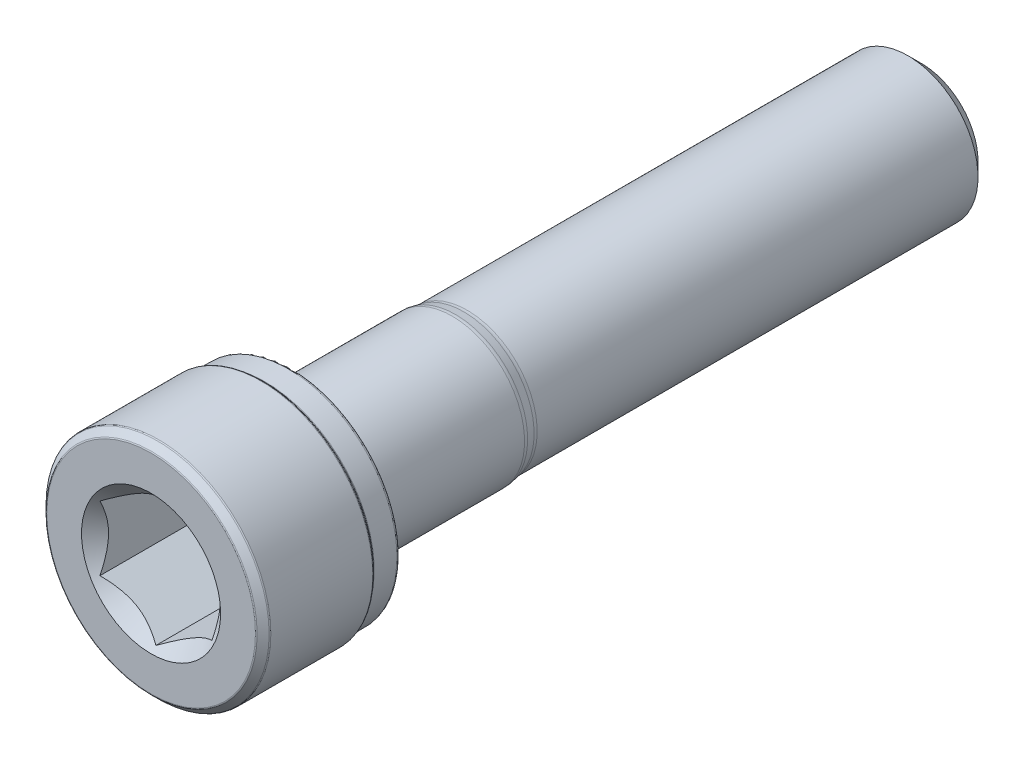
SolidWorks part; units mm, degrees
ref_plane "Front Plane" through (0, 0, 0) normal (0, 0, 1) x (1, 0, 0)
ref_plane "Top Plane" through (0, 0, 0) normal (0, 1, 0) x (1, 0, 0)
ref_plane "Right Plane" through (0, 0, 0) normal (1, 0, 0) x (0, 0, -1)
sketch "Sketch1" plane through (0, 0, 0) normal (1, 0, 0) x (0, 0, -1)
  line L0 (-27.5, 0) -> (27.5, 0) construction
  line L1 (27.5, 0) -> (27.5, 4.0257) construction
  line L2 (27.5, 4.0257) -> (26.5257, 5) construction
  line L3 (26.5257, 5) -> (26.375, 5) construction
  line L4 (26.375, 5) -> (-17.5, 5) construction
  line L5 (-17.5, 5) -> (-17.5, 8) construction
  line L6 (-17.5, 8) -> (-27.5, 8) construction
  line L7 (-27.5, 8) -> (-27.5, 0) construction
  line L8 (27.5, 4.0257) -> (27.5, 5) construction
  line L9 (27.4062, 5.1624) -> (28.1562, 3.8633) construction
  line L10 (28.1562, 3.8633) -> (28.9062, 5.1624) construction
  line L11 (28.9062, 5.1624) -> (27.4062, 5.1624) construction
  line L12 (28.1562, 5.1624) -> (28.1562, 5) construction
  line L13 (28.1562, 3.8633) -> (28.1562, 4.0257) construction
  line L14 (28.0625, 4.0257) -> (28.25, 4.0257) construction
  line L15 (27.5, 5) -> (28.8125, 5) construction
  line L16 (27.4531, 5.0812) -> (28.8594, 5.0812) construction
  line L17 (27.5, 0) -> (27.5, -5) construction
  line L18 (-18, 8) -> (-17.5, 7.5) construction
  line L19 (-27, 8) -> (-27.5, 7.5) construction
  line L20 (-17.5, 5) -> (-17.5, 0) construction
  line L21 (-17.5, 2.5) -> (-2.5, 2.5) construction
  line L22 (-2.5, 2.5) -> (12.5, 2.5) construction
  line L23 (12.5, 2.5) -> (27.5, 2.5) construction
  line L24 (-2.5, 2.5) -> (-2.5, 5) construction
  line L25 (-2.5, 5) -> (-2.5, 8) construction
  line L26 (12.5, 2.5) -> (12.5, 8) construction
  point P0 (-27.5, 4)
  point P3 (23.75, 5)
  point P4 (0, 0)
  point P18 (12.5, 5)
  point P22 (28.1562, 4.0257)
  point P24 (26.375, 5)
  point P25 (28.1562, 5)
  point P28 (28.1563, 5.0812)
  point P29 (23.75, -5)
  point P30 (-2.5, 5)
  point P31 (-22.5, 8)
  point P37 (-19.25, 8)
  point P38 (-26.75, 8)
  point P45 (-2.5, 2.5)
  point P46 (12.5, 2.5)
  point P49 (-4.5, 5)
  dimension "D1" = 45
  dimension "D2" = 0.1875
  dimension "D7" = 0.5
  dimension "D8" = 0.5
  dimension "D9" = 0.5
  dimension "D10" = 0.25
  dimension "D11" = 1.25
  dimension "Drive Size" = 8
  dimension "Head Diameter" = 16
  dimension "Head Height" = 10
  dimension "Thread Pitch" = 1.5
  dimension "Thread Dia" = 10
  dimension "Length" = 45
  dimension "D12" = 1.125
  dimension "D4" = 3.75
  dimension "Minimum Thread Length" = 32
sketch "Sketch2" plane through (0, 0, 0) normal (1, 0, 0) x (0, 0, -1)
  line L0 (-27.5, 0) -> (-27.5, 7.4482)
  line L1 (-26.9482, 8) -> (-19.6768, 8)
  line L2 (-17.5, 7.55) -> (-17.5, 5.6624)
  line L4 (26.5257, 5) -> (27.5, 4.0257)
  line L5 (27.5, 4.0257) -> (27.5, 0)
  line L6 (-17.5, 8) -> (-27.5, 8) construction
  line L7 (27.5, 0) -> (-27.5, 0)
  line L8 (-27, 8) -> (-27.5, 7.5) construction
  line L10 (-27.0366, 7.9634) -> (-27.4634, 7.5366)
  line L12 (-19.3232, 7.75) -> (-17.7, 7.75)
  line L14 (-18, 8) -> (-17.5, 7.5) construction
  line L15 (-19.5884, 7.9634) -> (-19.4116, 7.7866)
  line L17 (-17.5, 5) -> (-17.5, 8) construction
  line L18 (-17, 5.1624) -> (-6.002, 5.1624)
  line L19 (-4.9394, 5) -> (26.5257, 5)
  line L20 (26.375, 5) -> (-17.5, 5) construction
  line L21 (-5.7581, 5.1384) -> (-5.1832, 5.024)
  line L22 (28.9062, 5.1624) -> (27.4062, 5.1624) construction
  arc A0 (-17.7, 7.75) -> (-17.5, 7.55) centre (-17.7, 7.55) cw
  arc A1 (-17.5, 5.6624) -> (-17, 5.1624) centre (-17, 5.6624) ccw
  arc A2 (-6.002, 5.1624) -> (-5.7581, 5.1384) centre (-6.002, 3.9124) cw
  arc A3 (-5.1832, 5.024) -> (-4.9394, 5) centre (-4.9394, 6.25) ccw
  arc A4 (-27.0366, 7.9634) -> (-26.9482, 8) centre (-26.9482, 7.875) cw
  arc A5 (-27.4634, 7.5366) -> (-27.5, 7.4482) centre (-27.375, 7.4482) ccw
  arc A6 (-19.5884, 7.9634) -> (-19.6768, 8) centre (-19.6768, 7.875) ccw
  arc A7 (-19.4116, 7.7866) -> (-19.3232, 7.75) centre (-19.3232, 7.875) ccw
  point P22 (-17.75, 7.75)
  point P39 (-5.0625, 5)
  point P47 (-19.375, 7.75)
  dimension "D2" = 0.2
  dimension "D3" = 0.5
  dimension "D6" = 1.25
  dimension "D7" = 0.125
  dimension "D1" = 1.875
  dimension "D4" = 11.25
  dimension "D5" = 0.5625
  dimension "D8" = 10.998
revolve "Revolve1" add sketch "Sketch2" angle 360 about L7
sketch "Sketch3" plane through (0, 0, 27.5) normal (0, 0, 1) x (1, 0, 0)
  line L1 (4, -2.3094) -> (4, 2.3094)
  line L2 (4, 2.3094) -> (0, 4.6188)
  line L3 (0, 4.6188) -> (-4, 2.3094)
  line L4 (-4, 2.3094) -> (-4, -2.3094)
  line L5 (-4, -2.3094) -> (0, -4.6188)
  line L6 (0, -4.6188) -> (4, -2.3094)
  circle A0 centre (0, 0) radius 4 construction
  circle A1 centre (0, 0) radius 8 construction
  circle A2 centre (0, 0) radius 8 construction
  circle A3 centre (0, 0) radius 4.6188 construction
  dimension "D1" = 9.2376
extrude "Cut-Extrude1" cut sketch "Sketch3" against normal offset from surface (9 mm away) 1 up to face at (-7.55, 0, 17.5)
sketch "Sketch4" plane through (0, 0, 27.5) normal (0, 0, 1) x (1, 0, 0)
  circle A0 centre (0, 0) radius 4.9652
  dimension "D1" = 9.9304
extrude "Cut-Extrude2" cut sketch "Sketch4" against normal up to vertex (5 mm away) draft 45 up to point (0, 8, 22.5)
sketch "Sketch11" plane through (0, 0, 0) normal (1, 0, 0) x (0, 0, -1)
  line L0 (-27.5, 0) -> (27.5, 0) construction
  line L1 (-27.5, 0) -> (27.5, 0) construction
  line L2 (-8.0641, -5) -> (-8.0641, 5) construction
  line L3 (26.375, 5) -> (-17.5, 5) construction
  line L4 (-14.7505, -5) -> (-14.7505, 5) construction
  line L5 (-6.002, 5.1624) -> (-6.002, -5.1624) construction
  point P7 (-8.0641, 0)
  point P10 (-14.7505, 0)
  dimension "D1" = 2.7495
  dimension "D2" = 2.0621
sketch "Sketch6" [suppressed] plane through (0, 0, -27.5) normal (0, 0, -1) x (-1, 0, 0)
  circle A0 centre (0, 0) radius 5
curve "Helix/Spiral1" [suppressed] pitch 1.5 height 33.5 turns 22.3333
sketch "Sketch10" [suppressed] plane through (0, 0, 0) normal (1, 0, 0) x (0, 0, -1)
  line L0 (-4.5, -5) -> (-4.5, 5)
  line L2 (-27.5, 0) -> (27.5, 0) construction
  point P3 (-4.5, 0)
split "Split1" [suppressed] bodies to split 106
sketch "Sketch7" [suppressed] plane through (0, 0, 0) normal (1, 0, 0) x (0, 0, -1)
  line L0 (27.4531, 5.0812) -> (28.8594, 5.0812)
  line L1 (28.8594, 5.0812) -> (28.25, 4.0257)
  line L2 (28.25, 4.0257) -> (28.0625, 4.0257)
  line L3 (28.0625, 4.0257) -> (27.4531, 5.0812)
sweep "Cut-Sweep1" [suppressed] cut profiles "Sketch7" path "Helix/Spiral1"
sketch "Sketch8" [suppressed] plane through (0, 0, 0) normal (1, 0, 0) x (0, 0, -1)
  line L0 (-17.5, 0) -> (-17.5, 5)
  line L2 (-17.5, 5) -> (-4.5, 5)
  line L4 (-4.5, 5) -> (-1.6132, 0)
  line L5 (-1.6132, 0) -> (-17.5, 0)
  line L6 (26.375, 5) -> (-17.5, 5) construction
  line L7 (-27.5, 0) -> (27.5, 0) construction
  dimension "D1" = 60
  dimension "D2" = 32
revolve "Revolve2" [suppressed] add sketch "Sketch8" angle 360 about L5
sketch "Sketch9" [suppressed] plane through (0, 0, 27.5) normal (0, 0, 1) x (1, 0, 0)
  line L0 (-0.0365, 7.8315) -> (-0.2, 8.1966)
  line L1 (-0.2, 8.1966) -> (0.2, 8.1966)
  line L2 (0.2, 8.1966) -> (0.0365, 7.8315)
  line L3 (0, 8) -> (0, 7.5) construction
  line L4 (0, 0) -> (-0.2, 8.1966) construction
  line L5 (0.2, 8.1966) -> (0, 0) construction
  circle A0 centre (0, 0) radius 7.75 construction
  arc A4 (-0.0365, 7.8315) -> (0.0365, 7.8315) centre (0, 7.8479) ccw
  point P10 (0, 7.75)
  point P19 (0, 7.75)
  dimension "D2" = 0.04
  dimension "D1" = 0.4
  dimension "D3" = 2.796
extrude "Cut-Extrude3" [suppressed] cut sketch "Sketch9" against normal through all
pattern_circular "CirPattern1" [suppressed] count 80 over 360 of bodies 112
equation "\"D2@Sketch1\" = \"Thread Pitch@Sketch1\" / 8"
equation "\"D4@Helix/Spiral1\" = \"Thread Pitch@Sketch1\""
equation "\"D7@Sketch1\" = \"Head Height@Sketch1\" * .05"
equation "\"D8@Sketch1\"=\"D7@Sketch1\""
equation "\"D9@Sketch1\"=\"D7@Sketch1\""
equation "\"D10@Sketch1\"=\"D7@Sketch1\"/2"
equation "\"D11@Sketch1\"=\"D10@Sketch1\"*5"
equation "\"D4@Sketch1\"=\"Thread Pitch@Sketch1\"*2.5"
equation "\"D12@Sketch1\"=\"Thread Pitch@Sketch1\"*.75"
equation "\"D3@Helix/Spiral1\"=\"Minimum Thread Length@Sketch1\"+\"Thread Pitch@Sketch1\""
equation "\"D2@Sketch8\"=\"Minimum Thread Length@Sketch1\""
equation "\"D1@Sketch2\"=\"Head Height@Sketch1\"*0.1875"
equation "\"D2@Sketch2\"=\"Head Diameter@Sketch1\"*0.0125"
equation "\"D3@Sketch2\"=\"Thread Dia@Sketch1\"*0.05"
equation "\"D1@Sketch9\"=\"Head Diameter@Sketch1\"*0.025"
equation "\"D2@Sketch9\"=\"D1@Sketch9\"*0.1"
equation "\"D1@CirPattern1\"=int ((360/\"D3@Sketch9\")*0.625)"
equation "\"D5@Sketch2\"=\"D12@Sketch1\"*0.5"
equation "\"D6@Sketch2\"=\"Thread Dia@Sketch1\"*0.125"
equation "\"D7@Sketch2\"=\"D8@Sketch1\"*0.25"
equation "\"D1@Sketch11\"=\"D8@Sketch2\"*0.25"
equation "\"D2@Sketch11\"=\"D8@Sketch2\"*0.1875"
equation "\"D1@Sketch4\"=\"D1@Sketch3\"*1.075"
